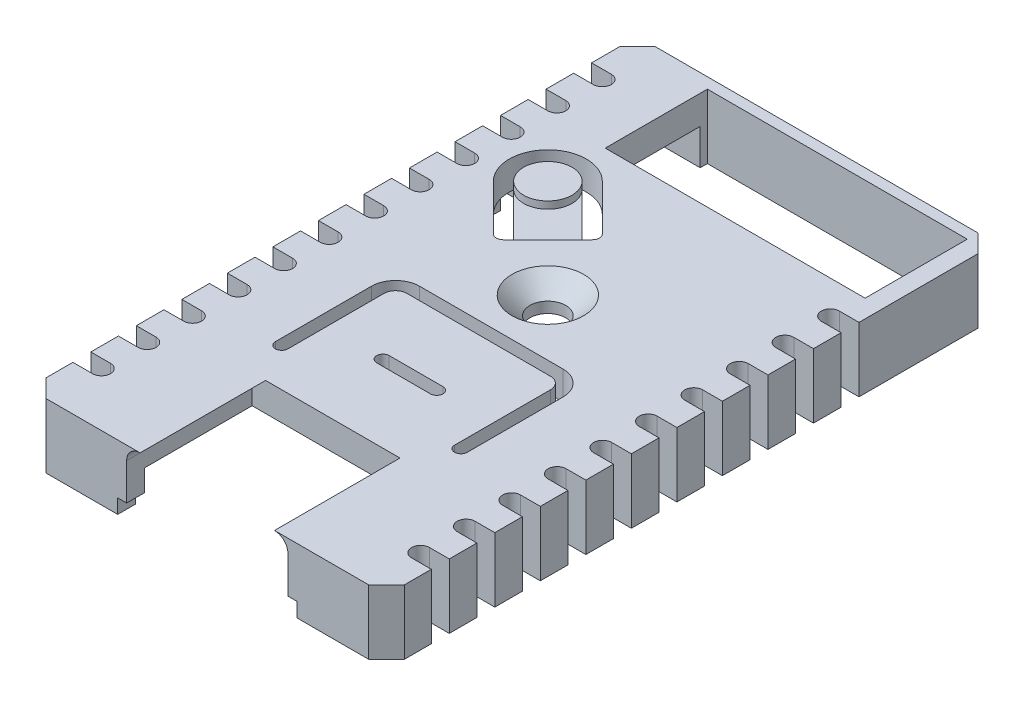
SolidWorks part; units mm, degrees
material "PP Copolymer"
ref_plane "Front Plane" through (0, 0, 0) normal (0, 0, 1) x (1, 0, 0)
ref_plane "Top Plane" through (0, 0, 0) normal (0, 1, 0) x (1, 0, 0)
ref_plane "Right Plane" through (0, 0, 0) normal (1, 0, 0) x (0, 0, -1)
sketch "BaseS" plane through (0, 0, 0) normal (0, 1, 0) x (1, 0, 0)
  line L1 (-10, 17) -> (10, 17)
  line L2 (-10, 17) -> (-10, -17)
  line L3 (-10, -17) -> (10, -17)
  line L4 (10, 17) -> (10, -17)
  line L5 (-10, 17) -> (10, -17) construction
  line L6 (-10, -17) -> (10, 17) construction
  point P0 (0, 0)
  dimension "Width" = 20
  dimension "Length" = 34
extrude "Base" add sketch "BaseS" against normal blind 1.6
chamfer "BaseChamfer" distance 1 angle 45 4 edges at (-10, -0.8, 17) (-10, -0.8, -17) (10, -0.8, -17) (10, -0.8, 17)
sketch "SideWallS" plane through (0, -1.6, 0) normal (0, -1, 0) x (1, 0, 0)
  line L0 (-9, 15.5858) -> (-9, -15.5858)
  line L1 (-9, -15.5858) -> (-8.5858, -16)
  line L2 (-8.5858, -16) -> (8.5858, -16)
  line L3 (8.5858, -16) -> (9, -15.5858)
  line L4 (9, -15.5858) -> (9, 15.5858)
  line L5 (9, 15.5858) -> (8.5858, 16)
  line L6 (8.5858, 16) -> (-8.5858, 16)
  line L7 (-8.5858, 16) -> (-9, 15.5858)
  line L8 (9, 17) -> (-9, 17)
  line L9 (-9, 17) -> (-10, 16)
  line L10 (-10, 16) -> (-10, -16)
  line L11 (-10, -16) -> (-9, -17)
  line L12 (-9, -17) -> (9, -17)
  line L13 (9, -17) -> (10, -16)
  line L14 (10, -16) -> (10, 16)
  line L15 (10, 16) -> (9, 17)
  line L16 (9, 17) -> (-9, 17)
  line L17 (-9, 17) -> (-10, 16)
  line L18 (-10, 16) -> (-10, -16)
  line L19 (-10, -16) -> (-9, -17)
  line L20 (-9, -17) -> (9, -17)
  line L21 (9, -17) -> (10, -16)
  line L22 (10, -16) -> (10, 16)
  line L23 (10, 16) -> (9, 17)
  dimension "D1" = 0
  dimension "Thickness" = 1
extrude "SideWall" add sketch "SideWallS" along normal blind 2
sketch "AntennaAccessS" plane through (0, 0, 0) normal (0, 1, 0) x (1, 0, 0)
  line L0 (9, 15.5858) -> (9, -15.5858) construction
  line L1 (-5.5, 16.4) -> (9, 16.4)
  line L2 (-5.5, 16.4) -> (-5.5, 10.7)
  line L3 (-5.5, 10.7) -> (9, 10.7)
  line L4 (9, 16.4) -> (9, 10.7)
  line L5 (-5.5, 16.4) -> (9, 10.7) construction
  line L6 (-5.5, 10.7) -> (9, 16.4) construction
  line L8 (9, 17) -> (-9, 17) construction
  point P0 (1.75, 13.55)
  dimension "Length" = 14.5
  dimension "Width" = 5.7
  dimension "YDim" = 0.6
extrude "AntennaAccess" cut sketch "AntennaAccessS" against normal through all
sketch "PinAccessS" plane through (0, 0, 0) normal (0, 1, 0) x (1, 0, 0)
  line L0 (-8.9, -14) -> (-10, -14) construction
  line L1 (-8.9, -14.5) -> (-10, -14.5)
  line L2 (-8.9, -13.5) -> (-10, -13.5)
  line L3 (-10, 16) -> (-10, -16) construction
  line L4 (-9, -17) -> (9, -17) construction
  arc A0 (-8.9, -14.5) -> (-8.9, -13.5) centre (-8.9, -14) ccw
  arc A1 (-10, -13.5) -> (-10, -14.5) centre (-10, -14) ccw
  point P2 (-9.45, -14)
  point P7 (-8.4, -14)
  dimension "Width" = 1
  dimension "Length" = 1.6
  dimension "YDim" = 3
extrude "PinAccess" cut sketch "PinAccessS" against normal through all
pattern_linear "PALP" count 12 spacing 2.54 along (0, 0, -1) of "PinAccess"
sketch "RightSidePinAccessS" plane through (0, 0, 0) normal (0, 1, 0) x (1, 0, 0)
  line L0 (0, 0) -> (0, -17) construction
  line L1 (-9, -17) -> (9, -17) construction
  line L5 (-8.9, -13.5) -> (-10, -13.5) construction
  line L6 (-8.9, -13.5) -> (-10, -13.5) construction
  line L7 (-8.9, -14.5) -> (-10, -14.5) construction
  line L8 (-8.9, -14.5) -> (-10, -14.5) construction
  line L9 (8.9, -14.5) -> (10, -14.5)
  line L10 (8.9, -13.5) -> (10, -13.5)
  arc A0 (-10, -13.5) -> (-10, -14.5) centre (-10, -14) ccw construction
  arc A1 (-10, -13.5) -> (-10, -14.5) centre (-10, -14) ccw construction
  arc A2 (-8.9, -14.5) -> (-8.9, -13.5) centre (-8.9, -14) ccw construction
  arc A3 (-8.9, -14.5) -> (-8.9, -13.5) centre (-8.9, -14) ccw construction
  arc A4 (8.9, -14.5) -> (8.9, -13.5) centre (8.9, -14) cw
  arc A5 (10, -13.5) -> (10, -14.5) centre (10, -14) cw
extrude "RightSidePinAccess" cut sketch "RightSidePinAccessS" against normal through all
pattern_linear "RSPALP" count 10 spacing 2.54 along (0, 0, -1) of "RightSidePinAccess"
sketch "FasteningHoleS" plane through (0, 0, 0) normal (0, 1, 0) x (1, 0, 0)
  line L0 (0, -17) -> (0, 2) construction
  line L1 (-9, -17) -> (9, -17) construction
  circle A0 centre (0, 2) radius 1
  dimension "Diameter" = 2
  dimension "YDim" = 19
extrude "FasteningHole" cut sketch "FasteningHoleS" against normal through all
sketch "MidSlitS" plane through (0, 0, 0) normal (0, 1, 0) x (1, 0, 0)
  line L0 (-1.5, -5.7) -> (1.5, -5.7) construction
  line L1 (-1.5, -5.35) -> (1.5, -5.35)
  line L2 (-1.5, -6.05) -> (1.5, -6.05)
  line L3 (0, -17) -> (0, -5.7) construction
  line L4 (-9, -17) -> (9, -17) construction
  arc A0 (-1.5, -5.35) -> (-1.5, -6.05) centre (-1.5, -5.7) ccw
  arc A1 (1.5, -6.05) -> (1.5, -5.35) centre (1.5, -5.7) ccw
  point P2 (0, -5.7)
  dimension "Width" = 0.7
  dimension "YDim" = 11.3
  dimension "Length" = 3
extrude "MidSlit" cut sketch "MidSlitS" against normal through all
sketch "HalfCurvedSlitS" plane through (0, 0, 0) normal (0, 1, 0) x (1, 0, 0)
  line L0 (-5, -8.2) -> (-5, -2.5) construction
  line L1 (-4, -1.5) -> (0, -1.5) construction
  line L2 (0, -1.5) -> (0, 0) construction
  line L3 (-4.65, -7.85) -> (-4.65, -2.5)
  line L4 (-4, -1.85) -> (0, -1.85)
  line L5 (0, -1.15) -> (-4, -1.15)
  line L6 (-5.35, -2.5) -> (-5.35, -7.85)
  arc A0 (-5, -2.5) -> (-4, -1.5) centre (-4, -2.5) cw construction
  arc A1 (-1.5, -5.35) -> (-1.5, -6.05) centre (-1.5, -5.7) ccw construction
  arc A2 (-5.35, -7.85) -> (-4.65, -7.85) centre (-5, -7.85) ccw
  arc A3 (0, -1.85) -> (0, -1.15) centre (0, -1.5) ccw
  arc A4 (-4.65, -2.5) -> (-4, -1.85) centre (-4, -2.5) cw
  arc A5 (-5.35, -2.5) -> (-4, -1.15) centre (-4, -2.5) cw
  dimension "Radius" = 1
  dimension "Diameter" = 0.7
  dimension "Width" = 5
  dimension "Length" = 6.7
  dimension "YDim" = 4.2
extrude "HalfCurvedSlit" cut sketch "HalfCurvedSlitS" against normal through all
mirror "HCSHM" about plane through (0, 0, 0) normal (1, 0, 0) of "HalfCurvedSlit"
sketch "ButtonSlitS" plane through (0, 0, 0) normal (0, 1, 0) x (1, 0, 0)
  line L0 (-3.909, 3.4341) -> (-6.7374, 6.2626) construction
  line L1 (-3.9797, 9.0203) -> (-1.4341, 6.4747)
  line L2 (-2.6716, 4.6716) -> (-3.909, 3.4341) construction
  line L3 (-10, 16) -> (-10, 14.44) construction
  line L4 (9, 17) -> (-9, 17) construction
  line L5 (-2.6716, 4.6716) -> (-5.5, 7.5) construction
  line L6 (-6.7374, 6.2626) -> (-4.1919, 3.717) construction
  line L7 (-6.4546, 6.5454) -> (-3.909, 3.9998)
  line L8 (-7.0203, 5.9797) -> (-4.4747, 3.4341)
  line L11 (-5.5, 7.5) -> (-7.0203, 9.0203) construction
  line L12 (-4.5454, 8.4546) -> (-1.9998, 5.909)
  arc A0 (-6.7374, 6.2626) -> (-6.7374, 8.7374) centre (-5.5, 7.5) cw construction
  arc A1 (-6.7374, 6.2626) -> (-6.7374, 8.7374) centre (-5.5, 7.5) cw construction
  arc A2 (-3.9797, 9.0203) -> (-7.0203, 5.9797) centre (-5.5, 7.5) ccw
  arc A3 (-4.5454, 8.4546) -> (-6.4546, 6.5454) centre (-5.5, 7.5) ccw
  arc A7 (-4.4747, 3.4341) -> (-3.909, 3.9998) centre (-4.1919, 3.717) ccw
  arc A10 (-1.4341, 6.4747) -> (-1.9998, 5.909) centre (-1.717, 6.1919) cw
  dimension "Radius" = 1.75
  dimension "XDim" = 4.5
  dimension "YDim" = 9.5
  dimension "Length" = 4
  dimension "Angle" = 45
  dimension "SlotWidth" = 0.8
extrude "ButtonSlit" cut sketch "ButtonSlitS" against normal through all
sketch "ButtonTabCutS" plane through (0, 0, 0) normal (0, 1, 0) x (1, 0, 0)
  line L0 (-4.5454, 8.4546) -> (-1.9998, 5.909) construction
  line L1 (-3.909, 3.9998) -> (-6.4546, 6.5454) construction
  line L2 (-4.5454, 8.4546) -> (-1.9998, 5.909)
  line L3 (-3.909, 3.9998) -> (-6.4546, 6.5454)
  line L4 (-1.9998, 5.909) -> (-3.909, 3.9998)
  arc A0 (-4.5454, 8.4546) -> (-6.4546, 6.5454) centre (-5.5, 7.5) ccw construction
  arc A2 (-4.5454, 8.4546) -> (-6.4546, 6.5454) centre (-5.5, 7.5) cw
extrude "ButtonTabCut" cut sketch "ButtonTabCutS" against normal blind 0.4
sketch "USBPortAccessS" plane through (0, 0, 17) normal (0, 0, 1) x (1, 0, 0)
  line L0 (3.75, 0) -> (-3.75, 0)
  line L1 (-9, 0) -> (9, 0) construction
  line L2 (0, 0) -> (0, -3.6) construction
  line L3 (9, -3.6) -> (-9, -3.6) construction
  line L4 (-4.5, -0.75) -> (-4.5, -2.8)
  line L5 (-4.5, -2.8) -> (-5, -2.8)
  line L6 (-5, -2.8) -> (-5, -3.6)
  line L7 (-5, -3.6) -> (5, -3.6)
  line L8 (5, -2.8) -> (5, -3.6)
  line L9 (4.5, -2.8) -> (5, -2.8)
  line L10 (4.5, -0.75) -> (4.5, -2.8)
  arc A0 (-3.75, 0) -> (-4.5, -0.75) centre (-3.75, -0.75) ccw
  arc A1 (3.75, 0) -> (4.5, -0.75) centre (3.75, -0.75) cw
  dimension "Radius" = 0.75
  dimension "Width" = 7.5
  dimension "BottomCutWidth" = 0.5
  dimension "BottomCutHeight" = 0.8
extrude "USBPortAccess" cut sketch "USBPortAccessS" against normal blind 7
chamfer "BTCC" distance 0.4 angle 45 1 edges at (-2.9544, 0, -4.9544)
chamfer "FHC" distance 1 angle 45 1 edges at (0, 0, -1)
